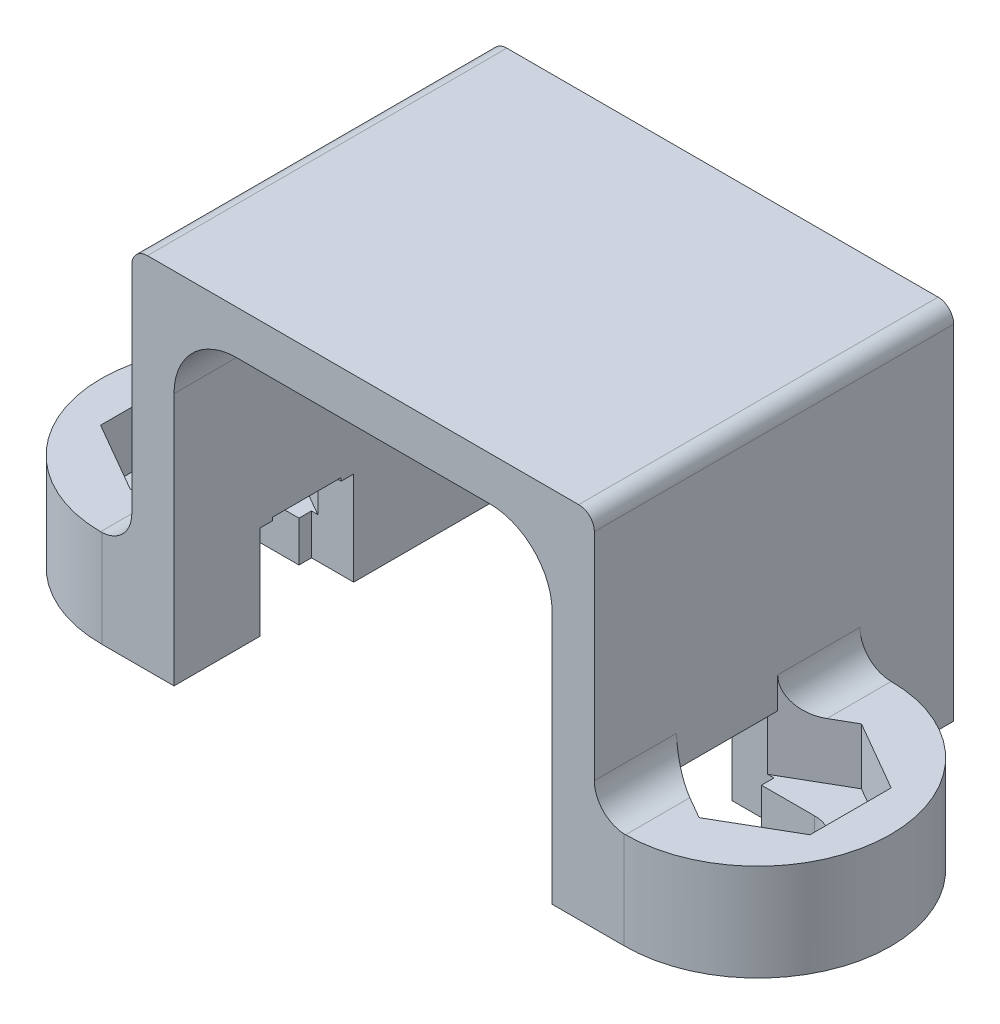
SolidWorks part; units mm, degrees
ref_plane "Front Plane" through (0, 0, 0) normal (0, 0, 1) x (1, 0, 0)
ref_plane "Top Plane" through (0, 0, 0) normal (0, 1, 0) x (1, 0, 0)
ref_plane "Right Plane" through (0, 0, 0) normal (1, 0, 0) x (0, 0, -1)
sketch "Sketch1" plane through (0, 0, 0) normal (0, 1, 0) x (1, 0, 0)
  line L1 (0, 5.75) -> (-7.4, 5.75)
  line L2 (0, 5.75) -> (0, -5.75)
  line L3 (0, -5.75) -> (-7.4, -5.75)
  line L4 (-7.4, 5.75) -> (-7.4, -5.75)
  dimension "D1" = 11.5
  dimension "D2" = 7.4
extrude "Boss-Extrude1" add sketch "Sketch1" along normal blind 11.5
sketch "Sketch3" plane through (0, 0, 0) normal (0, 1, 0) x (1, 0, 0)
  line L0 (0, -5.75) -> (-13.4687, -5.75) construction
  line L1 (0, -6.4181) -> (0, 6.1349) construction
  line L2 (-8.35, 2.7497) -> (-7.4, 2.7497)
  line L3 (-7.4, 5.75) -> (-7.4, -5.75) construction
  line L4 (-7.4, 2.7497) -> (-7.4, -5.75)
  line L5 (-7.4, -5.75) -> (-8.35, -5.75)
  line L6 (0, -5.75) -> (0, 5.75) construction
  arc A0 (-8.35, -5.75) -> (-8.35, 2.7497) centre (-8.383, -1.5001) cw
  dimension "D1" = 4.25
  dimension "D2" = 0.95
  dimension "D3" = 8.4997
extrude "Boss-Extrude2" add sketch "Sketch3" along normal blind 3.1
sketch "Sketch6" plane through (0, 0, -5.75) normal (0, 0, -1) x (-1, 0, 0)
  line L1 (0, 0) -> (6.05, 0)
  line L2 (0, 0) -> (0, 10.1)
  line L3 (0, 10.1) -> (6.05, 10.1)
  line L4 (6.05, 0) -> (6.05, 10.1)
  dimension "D1" = 6.05
  dimension "D2" = 10.1
extrude "Cut-Extrude1" cut sketch "Sketch6" against normal through all
sketch "Sketch7" plane through (0, 0, 0) normal (0, -1, 0) x (1, 0, 0)
  line L0 (-9.1, 1.5001) -> (-6.05, 1.5001) construction
  line L1 (-9.1, 2.6001) -> (-6.05, 2.6001)
  line L2 (-9.1, 0.4001) -> (-6.05, 0.4001)
  line L6 (-6.05, 5.75) -> (-6.05, -5.75) construction
  line L7 (-12.633, 1.5001) -> (0.5897, 1.5001) construction
  arc A0 (-9.1, 2.6001) -> (-9.1, 0.4001) centre (-9.1, 1.5001) ccw
  arc A1 (-6.05, 0.4001) -> (-6.05, 2.6001) centre (-6.05, 1.5001) ccw
  arc A2 (-8.35, 5.75) -> (-8.35, -2.7497) centre (-8.383, 1.5001) ccw construction
  point P2 (-7.575, 1.5001)
  dimension "D1" = 2.2
  dimension "D2" = 9.1
extrude "Cut-Extrude2" cut sketch "Sketch7" against normal up to surface (3.1 mm away) up to face at (-9.0645, 3.1, 2.5626)
sketch "Sketch8" plane through (-6.05, 0, 0) normal (1, 0, 0) x (0, 0, -1)
  line L0 (-2.6001, 0) -> (-0.4001, 0) construction
  line L1 (-3.0001, 3) -> (-0.0001, 3)
  line L2 (-3.0001, 3) -> (-3.0001, 0)
  line L3 (-3.0001, 0) -> (-0.0001, 0)
  line L4 (-0.0001, 3) -> (-0.0001, 0)
  line L5 (-1.5001, 0) -> (-1.5001, 3.8569) construction
  dimension "D1" = 3
  dimension "D2" = 3
extrude "Cut-Extrude3" cut sketch "Sketch8" against normal up to surface (1.35 mm away) up to face at (-7.4, 5.1437, -0.1062)
sketch "Sketch9" plane through (0, 3.1, 0) normal (0, 1, 0) x (1, 0, 0)
  line L0 (-10.2, -1.5001) -> (-9.1, -1.5001) construction
  line L2 (-6.85, -2.7992) -> (-6.85, -0.2011)
  line L3 (-6.85, -0.2011) -> (-9.1, 1.0979)
  line L4 (-9.1, 1.0979) -> (-11.35, -0.2011)
  line L5 (-11.35, -0.2011) -> (-11.35, -2.7992)
  line L6 (-11.35, -2.7992) -> (-9.1, -4.0982)
  line L7 (-9.1, -4.0982) -> (-6.85, -2.7992)
  arc A0 (-9.1, -0.4001) -> (-9.1, -2.6001) centre (-9.1, -1.5001) ccw construction
  circle A1 centre (-9.1, -1.5001) radius 2.25 construction
  dimension "D1" = 4.5
extrude "Cut-Extrude4" cut sketch "Sketch9" against normal blind 1.8
fillet "Fillet1" radius 1 2 edges
fillet "Fillet2" radius 0.5 1 edges at (-7.4, 11.5, 0)
fillet "Fillet3" radius 2 1 edges at (-6.05, 10.1, 0)
mirror "Mirror3" about plane through (0, 0, 0) normal (1, 0, 0) of "Cut-Extrude4", "Cut-Extrude3", "Cut-Extrude2", "Cut-Extrude1", "Boss-Extrude2", "Boss-Extrude1", "Fillet2", "Fillet3", "Fillet1"
